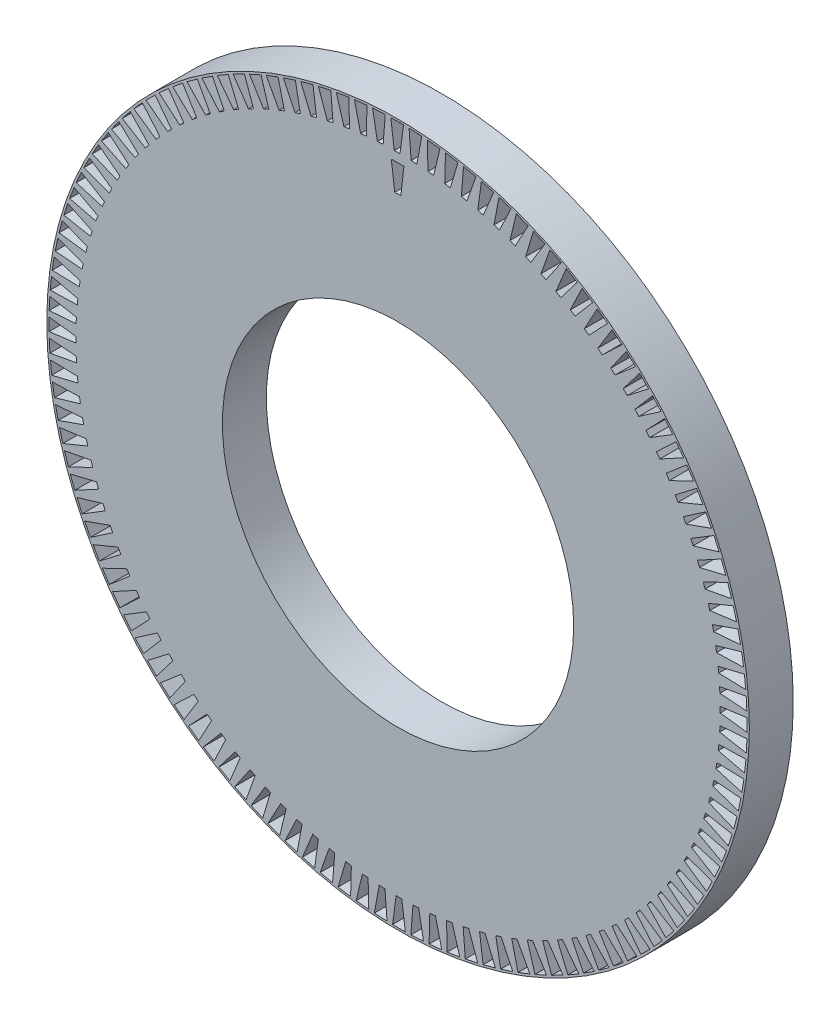
SolidWorks part; units mm, degrees
ref_plane "Front Plane" through (0, 0, 0) normal (0, 0, 1) x (1, 0, 0)
ref_plane "Top Plane" through (0, 0, 0) normal (0, 1, 0) x (1, 0, 0)
ref_plane "Right Plane" through (0, 0, 0) normal (1, 0, 0) x (0, 0, -1)
sketch "Sketch1" plane through (0, 0, 0) normal (0, 0, 1) x (1, 0, 0)
  circle A0 centre (0, 0) radius 40
  circle A1 centre (0, 0) radius 80
extrude "Boss-Extrude1" add sketch "Sketch1" along normal blind 10
sketch "Sketch2" plane through (0, 0, 10) normal (0, 0, 1) x (1, 0, 0)
  line L9 (-1.6535, 79.4785) -> (1.2419, 79.4785)
  line L10 (1.2419, 79.4785) -> (0.445, 73.3691)
  line L11 (0.445, 73.3691) -> (-0.8566, 73.3691)
  line L12 (-0.8566, 73.3691) -> (-1.6535, 79.4785)
  point P3 (-0.2058, 79.4785)
extrude "Cut-Extrude1" cut sketch "Sketch2" against normal blind 10
pattern_circular "CirPattern1" count 120 over 360 about axis through (0, 0, 10) along (0, 0, -1) of "Cut-Extrude1"
sketch "Sketch4" plane through (0, 0, 10) normal (0, 0, 1) x (1, 0, 0)
  line L14 (1.3388, 71.3527) -> (0.6404, 65.2099)
  line L16 (-0.7408, 65.1985) -> (-1.5405, 71.329)
  line L17 (-0.7408, 65.1985) -> (0.6404, 65.2099)
  line L18 (-1.5405, 71.329) -> (1.3388, 71.3527)
  line L19 (0, 0) -> (0, 90.788) construction
extrude "Cut-Extrude2" cut sketch "Sketch4" against normal blind 10
scale "Scale1" scale about centroid uniform scaling yes scale factor 0.15
